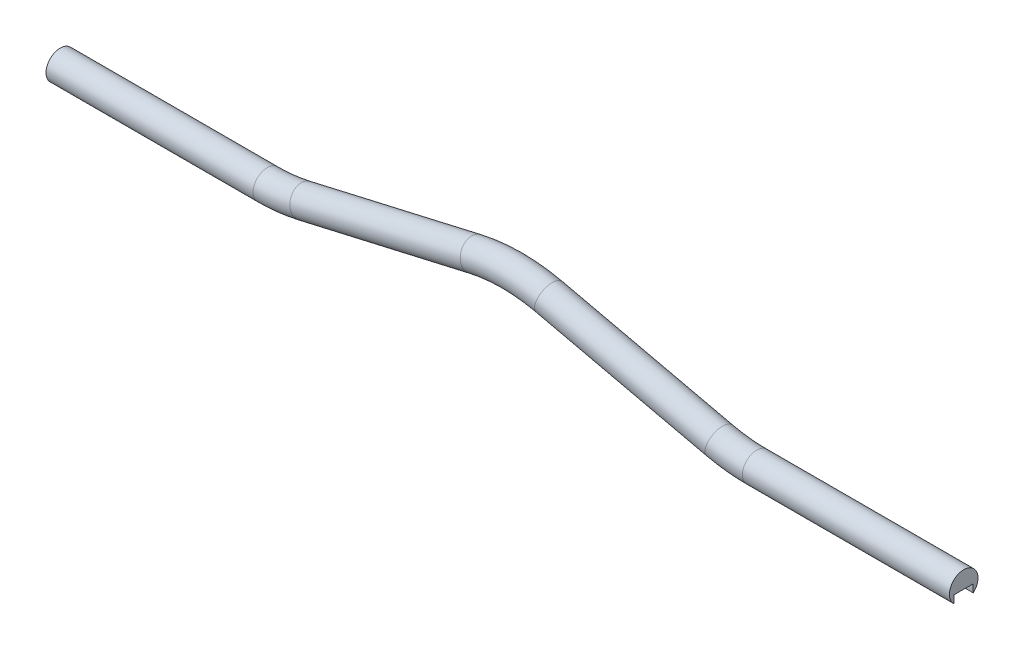
SolidWorks part; units mm, degrees
ref_plane "Front Plane" through (0, 0, 0) normal (0, 0, 1) x (1, 0, 0)
ref_plane "Top Plane" through (0, 0, 0) normal (0, 1, 0) x (1, 0, 0)
ref_plane "Right Plane" through (0, 0, 0) normal (1, 0, 0) x (0, 0, -1)
sketch "Sketch1" plane through (0, 0, 0) normal (0, 0, 1) x (1, 0, 0)
  line L0 (-475, 0) -> (-257.2802, 0)
  line L1 (-218.2217, 4.4273) -> (-39.0585, 45.5727)
  line L2 (0, 0) -> (0, 50) construction
  line L3 (218.2217, 4.4273) -> (39.0585, 45.5727)
  line L4 (475, 0) -> (257.2802, 0)
  arc A0 (257.2802, 0) -> (218.2217, 4.4273) centre (257.2802, 174.5036) cw
  arc A1 (39.0585, 45.5727) -> (-39.0585, 45.5727) centre (0, -124.5036) ccw
  arc A2 (-257.2802, 0) -> (-218.2217, 4.4273) centre (-257.2802, 174.5036) ccw
  point P7 (-475, 0)
  point P11 (237.5, 0)
  point P13 (0, 50)
  point P17 (-237.5, 0)
  dimension "D1" = 237.5
  dimension "D3" = 50
  dimension "D2" = 475
sweep "Sweep1" add path "Sketch1" circular profile diameter 30 parameters "D3"=30
sketch "Sketch26" plane through (-475, 0, 0) normal (-1, 0, 0) x (0, 0, 1)
  line L1 (-10, -27.1791) -> (10, -27.1791)
  line L2 (-10, -27.1791) -> (-10, -2.8209)
  line L3 (-10, -2.8209) -> (10, -2.8209)
  line L4 (10, -27.1791) -> (10, -2.8209)
  line L5 (-10, -27.1791) -> (10, -2.8209) construction
  line L6 (-10, -2.8209) -> (10, -27.1791) construction
  circle A0 centre (0, 0) radius 15 construction
  point P0 (0, -15)
extrude "Cut-Extrude2" cut sketch "Sketch26" against normal blind 237.5
extrude "Cut-Extrude3" cut sketch "Sketch26<2>" along normal blind 237.5 from surface starting at face at (475, -15, 0)
sketch "Sketch26<2>" plane through (-475, 0, 0) normal (-1, 0, 0) x (0, 0, 1) same geometry as "Sketch26"
